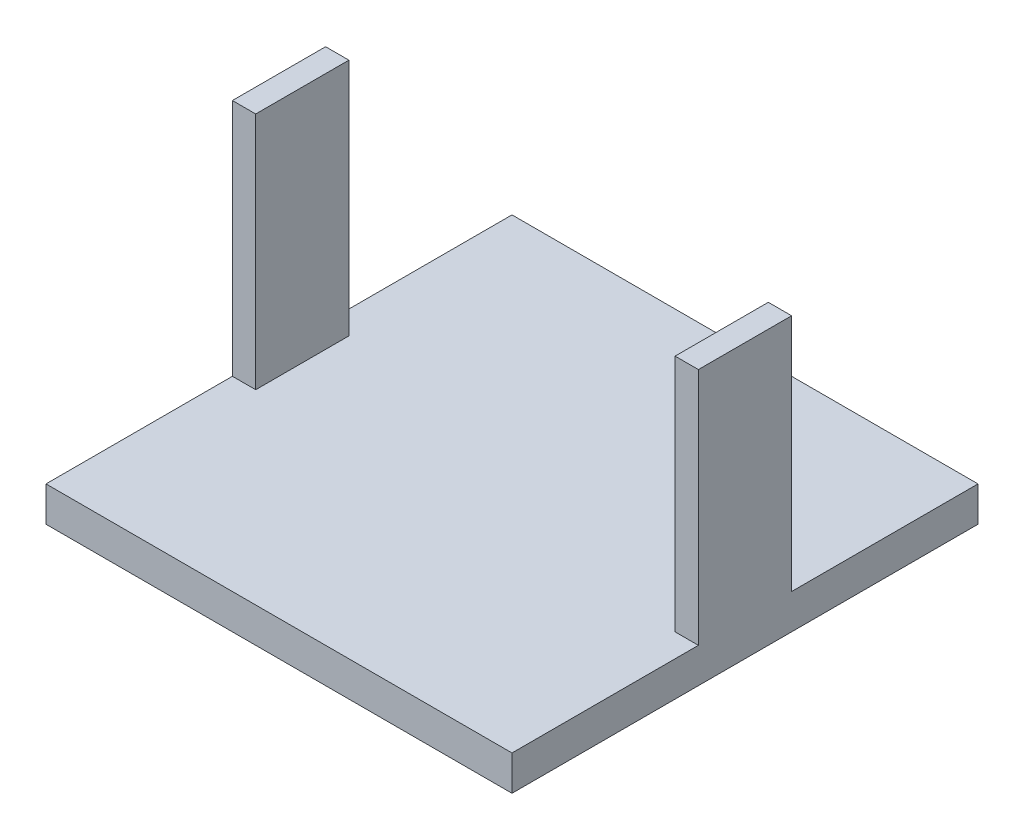
SolidWorks part; units mm, degrees
ref_plane "Plano frontal" through (0, 0, 0) normal (0, 0, 1) x (1, 0, 0)
ref_plane "Plano superior" through (0, 0, 0) normal (0, 1, 0) x (1, 0, 0)
ref_plane "Plano direito" through (0, 0, 0) normal (1, 0, 0) x (0, 0, -1)
sketch "Esboço1" plane through (0, 0, 0) normal (0, 1, 0) x (1, 0, 0)
  line L1 (0, 0) -> (400, 0)
  line L2 (0, 0) -> (0, 400)
  line L3 (0, 400) -> (400, 400)
  line L4 (400, 0) -> (400, 400)
  line L5 (0, 0) -> (20, 0)
  line L6 (0, 0) -> (0, 400)
  line L7 (0, 400) -> (20, 400)
  line L8 (20, 0) -> (20, 400)
  line L9 (400, 0) -> (380, 0)
  line L10 (400, 0) -> (400, 400)
  line L11 (400, 400) -> (380, 400)
  line L12 (380, 0) -> (380, 400)
extrude "Ressalto-extrusão1" add sketch "Esboço1" along normal blind 205 contours L1 L8 L3 L2 region at (10, 0, -200)
extrude "Ressalto-extrusão2" add sketch "Esboço1<3>" along normal blind 30 contours L1 L12 L3 L8 region at (200, 0, -200)
sketch "Esboço1<3>" plane through (0, 0, 0) normal (0, 1, 0) x (1, 0, 0) same geometry as "Esboço1"
extrude "Ressalto-extrusão3" add sketch "Esboço1<4>" along normal blind 205 contours L12 L1 L4 L3 region at (390, 0, -200)
sketch "Esboço1<4>" plane through (0, 0, 0) normal (0, 1, 0) x (1, 0, 0) same geometry as "Esboço1"
sketch "Esboço2" plane through (0, 205, 0) normal (0, 1, 0) x (1, 0, 0)
  line L1 (0, 400) -> (20, 400)
  line L2 (0, 400) -> (0, 0)
  line L3 (0, 0) -> (20, 0)
  line L4 (20, 400) -> (20, 0)
extrude "Ressalto-extrusão4" add sketch "Esboço2" along normal blind 30
sketch "Esboço3" plane through (0, 205, 0) normal (0, 1, 0) x (1, 0, 0)
  line L1 (400, 400) -> (380, 400)
  line L2 (400, 400) -> (400, 0)
  line L3 (400, 0) -> (380, 0)
  line L4 (380, 400) -> (380, 0)
extrude "Ressalto-extrusão5" add sketch "Esboço3" along normal blind 30
sketch "Esboço4" plane through (0, 235, 0) normal (0, 1, 0) x (1, 0, 0)
  line L0 (20, 0) -> (20, 400) construction
  line L1 (20, 200) -> (0, 200)
  line L2 (20, 200) -> (20, 240)
  line L3 (20, 240) -> (0, 240)
  line L4 (0, 200) -> (0, 240)
  line L5 (0, 400) -> (0, 0) construction
  line L7 (20, 200) -> (0, 200)
  line L8 (20, 200) -> (20, 160)
  line L9 (20, 160) -> (0, 160)
  line L10 (0, 200) -> (0, 160)
  line M1 (0, 400) -> (0, 0)
  line M2 (0, 0) -> (20, 0)
  line M3 (20, 0) -> (20, 400)
  line M4 (20, 400) -> (0, 400)
extrude "Corte-extrusão1" cut sketch "Esboço4" against normal blind 205 contours L3 M3 M4 M1 | L9 M3 M1 M2 region at (10, 235, -320) region at (10, 235, -80)
sketch "Esboço5" plane through (0, 235, 0) normal (0, 1, 0) x (1, 0, 0)
  line L0 (380, 400) -> (380, 0) construction
  line L1 (380, 200) -> (400, 200)
  line L2 (380, 200) -> (380, 240)
  line L3 (380, 240) -> (400, 240)
  line L4 (400, 200) -> (400, 240)
  line L5 (400, 0) -> (400, 400) construction
  line L7 (380, 200) -> (400, 200)
  line L8 (380, 200) -> (380, 160)
  line L9 (380, 160) -> (400, 160)
  line L10 (400, 200) -> (400, 160)
  line M1 (400, 0) -> (400, 400)
  line M2 (400, 400) -> (380, 400)
  line M3 (380, 400) -> (380, 0)
  line M4 (380, 0) -> (400, 0)
extrude "Corte-extrusão2" cut sketch "Esboço5" against normal blind 205 contours L3 M3 M1 M2 | L9 M3 M4 M1 region at (390, 235, -320) region at (390, 235, -80)
